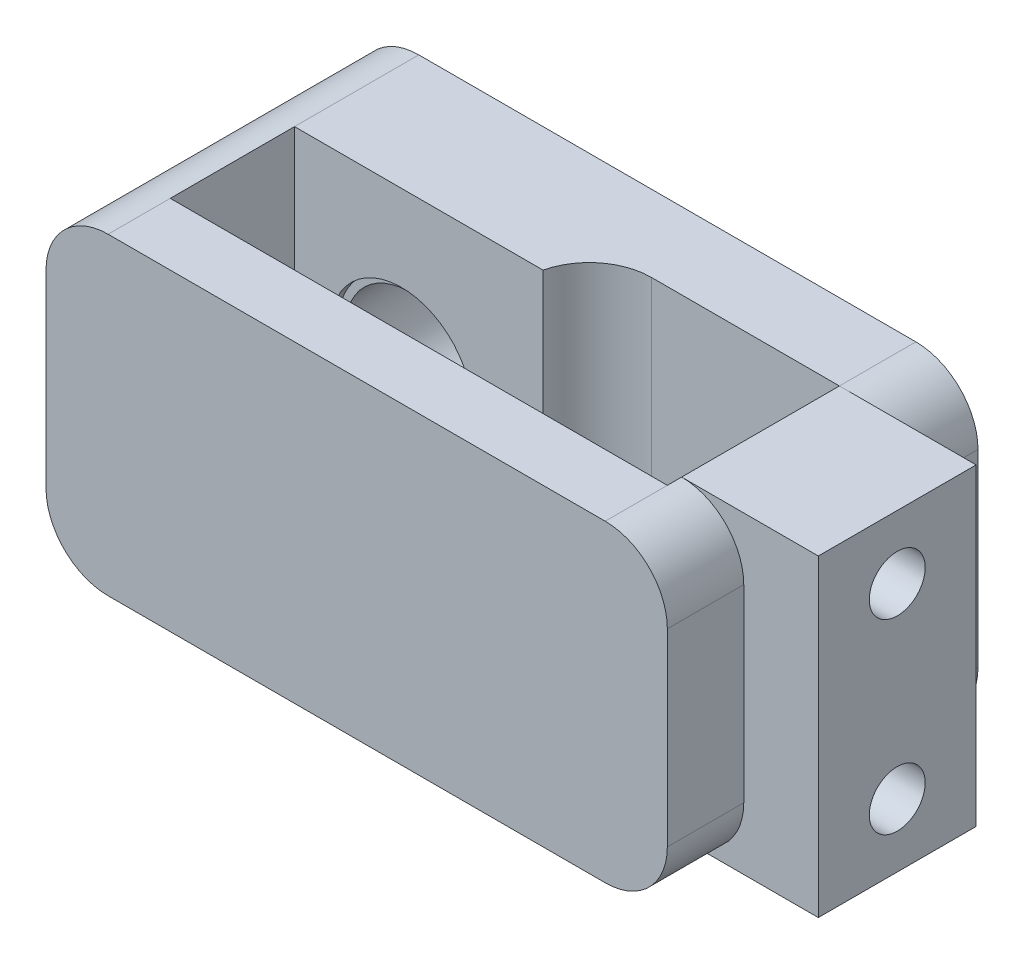
SolidWorks part; units mm, degrees
ref_plane "Front Plane" through (0, 0, 0) normal (0, 0, 1) x (1, 0, 0)
ref_plane "Top Plane" through (0, 0, 0) normal (0, 1, 0) x (1, 0, 0)
ref_plane "Right Plane" through (0, 0, 0) normal (1, 0, 0) x (0, 0, -1)
sketch "Sketch1" plane through (0, 0, 0) normal (0, 1, 0) x (1, 0, 0)
  line L1 (-20, 2.5) -> (20, 2.5)
  line L2 (-20, 2.5) -> (-20, -7.5)
  line L3 (-20, -7.5) -> (20, -7.5)
  line L4 (20, 2.5) -> (20, -7.5)
  line L7 (-25, 12.5) -> (25, 12.5)
  line L8 (-25, 12.5) -> (-25, -12.5)
  line L9 (-25, -12.5) -> (25, -12.5)
  line L10 (25, 12.5) -> (25, -12.5)
  point P0 (0, 0)
  point P6 (0, -7.5)
  point P7 (0, 0)
  point P12 (0, -12.5)
  point P13 (25, 0)
  point P14 (-20, 2.5)
  dimension "D1" = 5
  dimension "D2" = 10
  dimension "D3" = 50
  dimension "D4" = 25
  dimension "D5" = 5
extrude "Boss-Extrude1" add sketch "Sketch1" along normal blind 25.2
sketch "Sketch4" plane through (0, 0, -2.5) normal (0, 0, 1) x (1, 0, 0)
  line L0 (-25, 25.2) -> (-25, 0) construction
  point P0 (-11.4, 12.6)
  point P7 (-25, 12.6)
  dimension "D1" = 13.6
sketch "Sketch9" plane through (20, 0, 0) normal (-1, 0, 0) x (0, 0, 1)
  line L0 (0, 20.1) -> (0, 5.1) construction
  line L2 (12.5, 25.2) -> (12.5, 0) construction
  point P0 (0, 20.1)
  point P2 (0, 5.1)
  point P11 (12.5, 12.6)
  point P12 (0, 12.6)
  dimension "D1" = 15
hole_wizard "Hole1" positions "Sketch4" profile "Sketch3" legacy end condition up to next
sketch "Sketch3" plane through (-11.4, 12.6, -2.5) normal (1, 0, 0) x (0, -1, 0)
  line L0 (0, 0) -> (0, 10)
  line L1 (0, 10) -> (5.1, 10)
  line L2 (5.1, 10) -> (5.1, 0.6)
  line L3 (5.1, 0.6) -> (5.7, 0.6)
  line L4 (5.7, 0.6) -> (5.7, 0)
  line L5 (5.7, 0) -> (0, 0)
  line L6 (0, 110) -> (0, -10) construction
  dimension "Diameter" = 10.2
  dimension "Depth" = 10
  dimension "C-Bore Diameter" = 11.4
  dimension "C-Bore Depth" = 0.6
sketch "Sketch10" plane through (25, 0, 0) normal (1, 0, 0) x (0, 0, -1)
  line L0 (-12.5, 25.2) -> (12.5, 25.2) construction
  line L1 (-6.35, 25.2) -> (6.35, 25.2)
  line L2 (-6.35, 25.2) -> (-6.35, 0)
  line L3 (-6.35, 0) -> (6.35, 0)
  line L4 (6.35, 25.2) -> (6.35, 0)
  line L5 (-12.5, 0) -> (12.5, 0) construction
  point P8 (0, 0)
  dimension "D1" = 12.7
extrude "Boss-Extrude2" add sketch "Sketch10" along normal blind 6
hole_wizard "M4 Clearance Hole1" positions "Sketch9" profile "Sketch8" hole size "M4" standard "ANSI Metric" end condition through all
sketch "Sketch8" plane through (20, 20.1, 0) normal (0, 1, 0) x (0, 0, 1)
  line L0 (0, 0) -> (0, 11)
  line L1 (0, 11) -> (2.25, 11)
  line L2 (2.25, 11) -> (2.25, 0.025)
  line L3 (2.25, 0.025) -> (2.275, 0)
  line L5 (2.275, 0) -> (0, 0)
  line L6 (-2.25, 0.025) -> (-2.275, 0) construction
  line L11 (0, -6.35) -> (0, 107.95) construction
  dimension "Thru Hole Dia." = 4.5
  dimension "Thru Hole Depth" = 11
  dimension "Near C'Sink Dia." = 4.55
  dimension "Near C'Sink Angle" = 90
sketch "Sketch11" plane through (0, 25.2, 0) normal (0, 1, 0) x (1, 0, 0)
  line L1 (20, 2.5) -> (0, 2.5)
  line L2 (20, 2.5) -> (20, 6.35)
  line L3 (20, 6.35) -> (0, 6.35)
  line L4 (0, 2.5) -> (0, 6.35)
  point P6 (0, 0)
  point P8 (0, 0)
  point P9 (20, 2.5)
  point P11 (0, 0)
extrude "Cut-Extrude1" cut sketch "Sketch11" against normal through all
fillet "Fillet1" radius 5 7 edges at (25, 0, -9.425) (25, 25.2, -9.425) (25, 0, 9.425) (25, 25.2, 9.425) (-25, 0, 0) (0, 12.6, -6.35) (-25, 25.2, 0)
